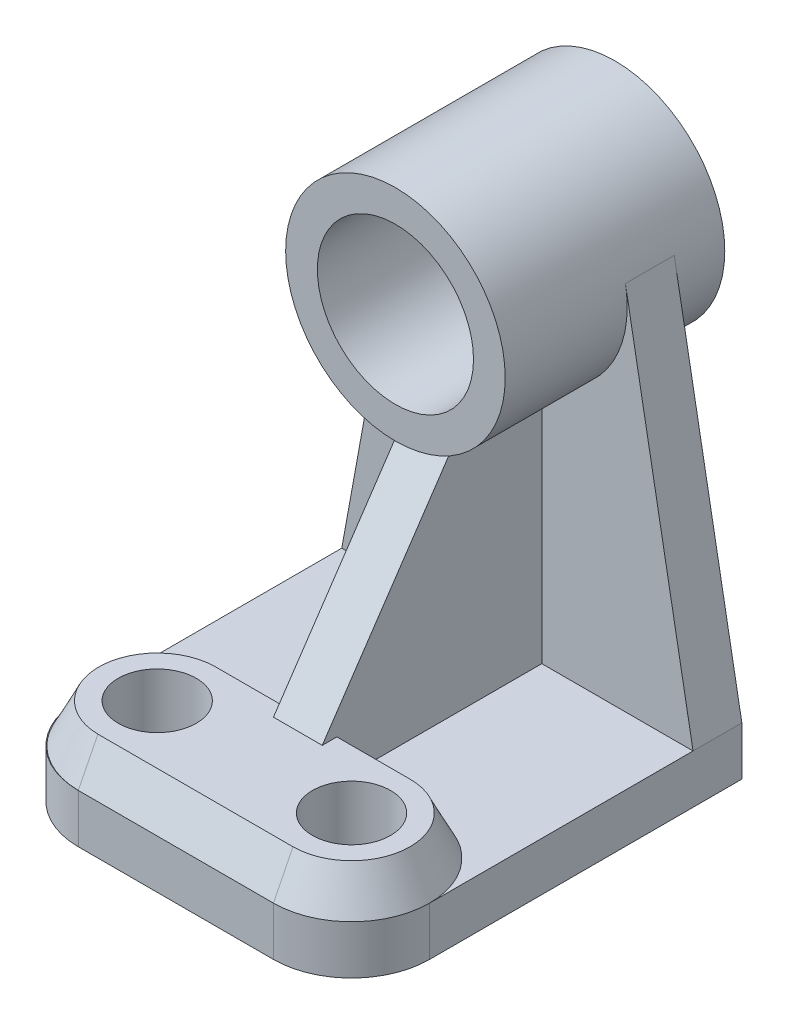
SolidWorks part; units mm, degrees
ref_plane "Front Plane" through (0, 0, 0) normal (0, 0, 1) x (1, 0, 0)
ref_plane "Top Plane" through (0, 0, 0) normal (0, 1, 0) x (1, 0, 0)
ref_plane "Right Plane" through (0, 0, 0) normal (1, 0, 0) x (0, 0, -1)
sketch "Sketch1" plane through (0, 0, 0) normal (0, 0, 1) x (1, 0, 0)
  line L0 (-36, -5) -> (36, -5)
  line L1 (-36, -5) -> (-36, 5)
  line L2 (36, -5) -> (36, 5)
  line L3 (-36, 5) -> (36, 5)
  line L4 (-36, -5) -> (36, 5) construction
  line L5 (36, -5) -> (-36, 5) construction
  line L6 (0, 0) -> (0, 77) construction
  line L7 (22.135, 81.0363) -> (36, 5)
  line L8 (-22.135, 81.0363) -> (-36, 5)
  circle A0 centre (0, 77) radius 22.5
  point P1 (0, 0)
  dimension "D4" = 45
  dimension "D1" = 82
  dimension "D2" = 72
  dimension "D3" = 10
extrude "Boss-Extrude1" add sketch "Sketch1" along normal blind 80 contours L3 L1 L0 L2 region at (0, 0, 0)
extrude "Boss-Extrude2" add sketch "Sketch1<3>" along normal blind 10 contours A0 L8 L3 L7 region at (0, 31.611, 0)
sketch "Sketch1<3>" plane through (0, 0, 0) normal (0, 0, 1) x (1, 0, 0) same geometry as "Sketch1"
extrude "Boss-Extrude3" add sketch "Sketch1<4>" along normal blind 35 and the other way blind 10 contours A0 region at (0, 77, 0)
sketch "Sketch1<4>" plane through (0, 0, 0) normal (0, 0, 1) x (1, 0, 0) same geometry as "Sketch1"
sketch "Sketch2" plane through (0, 5, 0) normal (0, 1, 0) x (1, 0, 0)
  line L0 (-20, -80) -> (20, -80)
  line L7 (-20, -48) -> (20, -48)
  line L10 (-36, -80) -> (36, -80) construction
  arc A0 (20, -80) -> (20, -48) centre (20, -64) ccw
  arc A1 (-20, -48) -> (-20, -80) centre (-19.8163, -64) ccw
  circle A2 centre (20, -64) radius 8
  circle A3 centre (-19.8163, -64) radius 8
  point P1 (0, -64)
  point P8 (0, -80)
  point P12 (0, -80)
  dimension "D2" = 32
  dimension "D3" = 16
  dimension "D1" = 40
extrude "Boss-Extrude4" add sketch "Sketch2" along normal blind 8
fillet "Fillet1" radius 16 2 edges at (-36, 0, 80) (36, 0, 80)
chamfer "Chamfer4" distance 8 distance2 4 4 edges at (36, 13, 64) (0, 13, 48) (-35.8173, 13, 64) (0, 13, 80) first distance on face at (27.7255, 8.2, 64) first distance on face at (0, 9, 48) first distance on face at (-27.9087, 9, 64) first distance on face at (0, 4.3333, 80)
extrude "Cut-Extrude2" cut sketch "Sketch2<3>" against normal through all contours A3 | A2 region at (20, 5, 64) region at (-19.8163, 5, 64)
sketch "Sketch2<3>" plane through (0, 5, 0) normal (0, 1, 0) x (1, 0, 0) same geometry as "Sketch2"
sketch "Sketch3" plane through (0, 0, 0) normal (1, 0, 0) x (0, 0, -1)
  line L0 (-55, 13) -> (-27, 54.5)
  line L1 (-52, 13) -> (-76, 13) construction
  line L2 (-35, 99.5) -> (-35, 54.5) construction
  line L3 (-10, 81.0363) -> (-10, 5) construction
  dimension "D1" = 8
  dimension "D2" = 45
rib "Rib1" sketch "Sketch3" sketch "Sketch3" thickness 10 extrusion direction parallel to sketch draft on no parameters "D1"=10
hole_wizard "CBORE for M5 Hex Head Bolt1" positions "Sketch6" profile "Sketch5" counterbore size "M5" standard "ISO"
sketch "Sketch6" plane through (0, 0, 35) normal (0, 0, 1) x (1, 0, 0)
  point P0 (0, 77)
sketch "Sketch5" plane through (0, 77, 35) normal (1, 0, 0) x (0, -1, 0)
  line L0 (0, 0) -> (0, 51.9282)
  line L1 (0, 51.9282) -> (12, 45)
  line L2 (12, 45) -> (12, 30)
  line L3 (12, 30) -> (16, 30)
  line L4 (16, 30) -> (16, 0)
  line L5 (16, 0) -> (0, 0)
  line L10 (0, 51.9282) -> (-12, 45) construction
  line L11 (0, -6.35) -> (0, 107.95) construction
  dimension "Hole Dia." = 24
  dimension "Hole Depth" = 45
  dimension "C'Bore Dia." = 32
  dimension "C'Bore Depth" = 30
  dimension "Drill Angle" = 120
